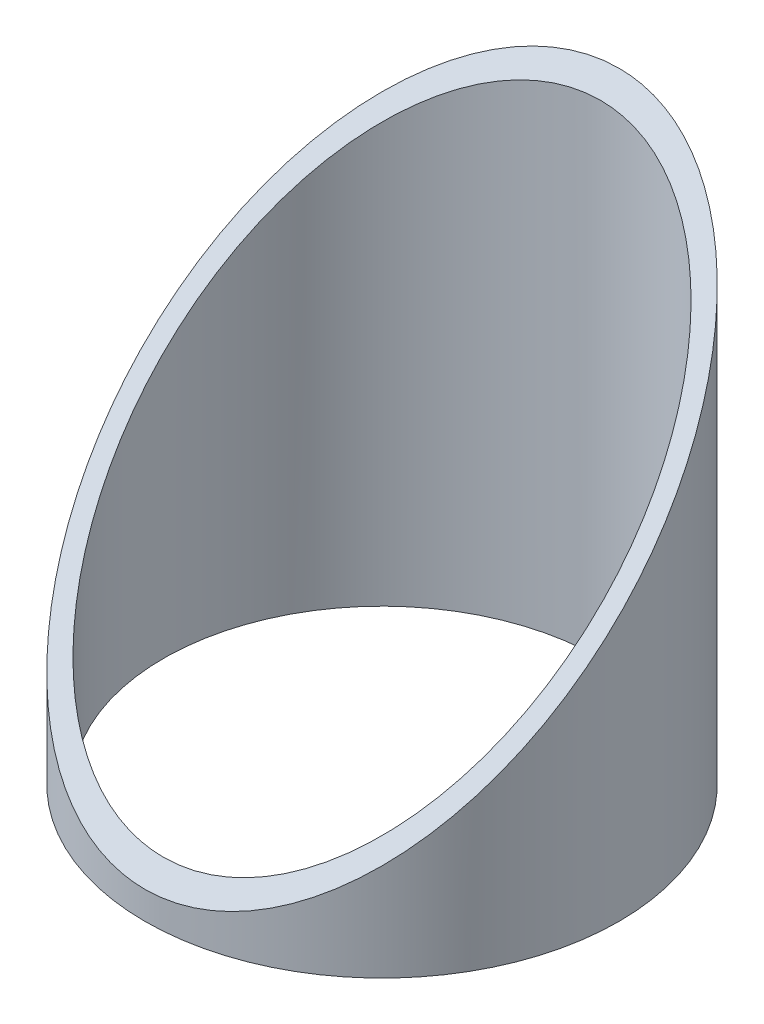
SolidWorks part; units mm, degrees
material "1060 Alloy"
ref_plane "Front Plane" through (0, 0, 0) normal (0, 0, 1) x (1, 0, 0)
ref_plane "Top Plane" through (0, 0, 0) normal (0, 1, 0) x (1, 0, 0)
ref_plane "Right Plane" through (0, 0, 0) normal (1, 0, 0) x (0, 0, -1)
sketch "Sketch1" plane through (0, 0, 0) normal (0, 1, 0) x (1, 0, 0)
  line L0 (-102.6662, 0) -> (114.9528, 0) construction
  line L1 (-55, 0) -> (55, 0) construction
ref_plane "Plane1" through (0, 0, 0) normal (0, 0.7071, 0.7071) x (1, 0, 0)
sketch "Sketch2" plane through (0, 0, 0) normal (0, 0.7071, 0.7071) x (1, 0, 0)
  circle A0 centre (0, 20) radius 20
  dimension "D1" = 40
extrude "Boss-Extrude1" add sketch "Sketch2" against normal blind 0.7071
ref_plane "Plane2" through (0, -3.25, 0) normal (0, 1, 0) x (1, 0, 0)
sketch "Sketch3" plane through (0, -3.25, 0) normal (0, 1, 0) x (1, 0, 0)
  line L0 (0, -15.8313) -> (0, 15.8313) construction
  circle A0 centre (0, 7.4) radius 7.4
  circle A1 centre (0, 7.4) radius 5.9
  dimension "D1" = 14.8
  dimension "D2" = 11.8
extrude "Boss-Extrude2" add sketch "Sketch3" along normal blind 1 separate body
sketch "Sketch4" plane through (0, -3.25, 0) normal (0, -1, 0) x (1, 0, 0)
  line L1 (-145.8552, 47.5561) -> (159.3648, 47.5561)
  line L2 (-145.8552, 47.5561) -> (-145.8552, -79.3149)
  line L3 (-145.8552, -79.3149) -> (159.3648, -79.3149)
  line L4 (159.3648, 47.5561) -> (159.3648, -79.3149)
  circle A3 centre (0, -7.4) radius 6.4
  circle A4 centre (0, -7.4) radius 7.4 construction
  dimension "D1" = 12.8
  dimension "D2" = 0
extrude "Cut-Extrude1" cut sketch "Sketch4" against normal through all both and the other way through all
sketch "Sketch5" plane through (0, -2.25, 0) normal (0, 1, 0) x (1, 0, 0)
  circle A1 centre (0, 7.4) radius 6.4
  circle A2 centre (0, 7.4) radius 7.4 construction
  circle A3 centre (0, 7.4) radius 5.9
  dimension "D1" = 12.8
  dimension "D3" = 11.8
  dimension "D2" = 0
extrude "Boss-Extrude3" add sketch "Sketch5" along normal up to next separate body
sketch "Sketch7" plane through (0, 0, 0) normal (0, 0.7071, 0.7071) x (1, 0, 0)
  circle A0 centre (0, 10.4652) radius 18.2827
extrude "Cut-Extrude3" cut sketch "Sketch7" against normal up to surface (0.7071 mm away) up to face at (0, 0, -1)
sketch "Sketch8" plane through (0, -3.25, 0) normal (0, -1, 0) x (1, 0, 0)
  circle A0 centre (0, -7.3953) radius 12.7728
extrude "Cut-Extrude4" cut sketch "Sketch8" against normal blind 2.5
